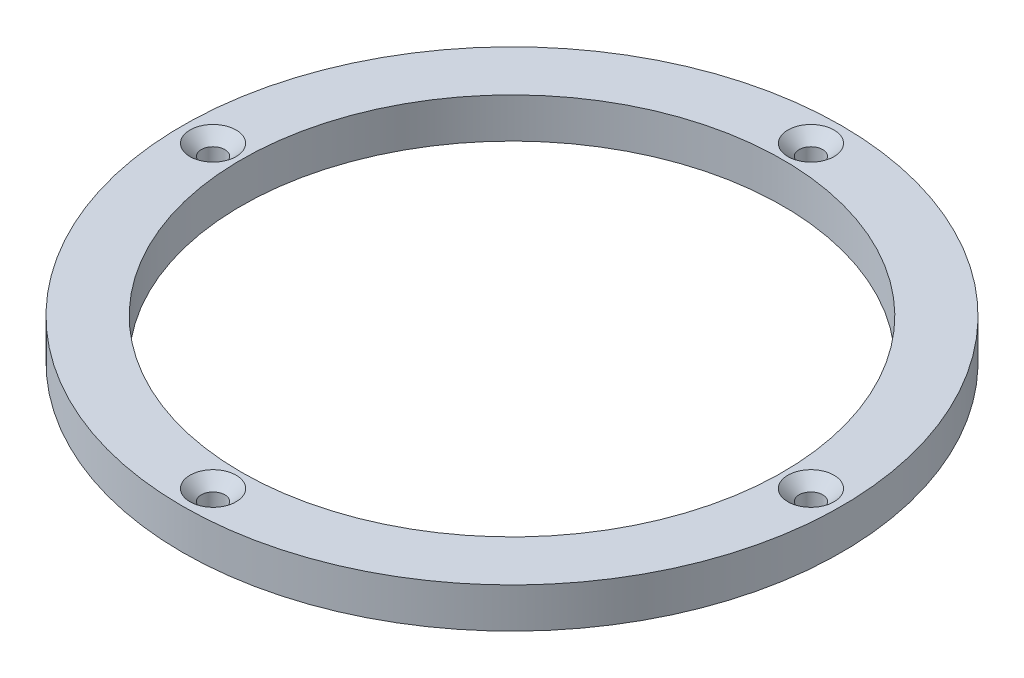
SolidWorks part; units mm, degrees
material "6061 合金"
ref_plane "前视基准面" through (0, 0, 0) normal (0, 0, 1) x (1, 0, 0)
ref_plane "上视基准面" through (0, 0, 0) normal (0, 1, 0) x (1, 0, 0)
ref_plane "右视基准面" through (0, 0, 0) normal (1, 0, 0) x (0, 0, -1)
other "Configuration Table"
sketch "草图1" plane through (0, 0, 0) normal (0, 1, 0) x (1, 0, 0)
  circle A0 centre (0, 0) radius 57.5
  circle A1 centre (0, 0) radius 70
  circle A2 centre (0, 0) radius 63.5 construction
  circle A3 centre (0, 63.5) radius 2.5
  circle A4 centre (63.5, 0) radius 2.5
  circle A5 centre (0, 0) radius 57.5
  circle A6 centre (0, -63.5) radius 2.5
  circle A7 centre (0, 0) radius 57.5
  circle A8 centre (-63.5, 0) radius 2.5
  circle A9 centre (0, 0) radius 57.5
  dimension "D1" = 127
  dimension "D2" = 140
  dimension "D3" = 115
  dimension "D4" = 5
  dimension "D5" = 4
extrude "凸台-拉伸1" add sketch "草图1" along normal blind 8.5 contours A1 A8 A6 A4 A3 A0 region at (-68.0201, 0, 0)
ref_axis "基准轴1" through (0, 8.5, -63.5) along (0, -1, 0)
ref_plane "基准面1" through (0, 0, -63.5) normal (0, 0, 1) x (1, 0, 0)
sketch "草图2" plane through (0, 0, -63.5) normal (0, 0, 1) x (1, 0, 0)
  line L0 (0, 0) -> (0, 8.5) construction
  line L1 (2.5, 8.5) -> (-2.5, 8.5) construction
  line L2 (0, 8.5) -> (4.9, 8.5)
  line L3 (70, 8.5) -> (-70, 8.5) construction
  line L4 (4.9, 8.5) -> (1.6, 5.2)
  line L5 (1.6, 5.2) -> (0, 5.2)
  line L6 (0, 5.2) -> (0, 8.5)
  dimension "D1" = 4.9
  dimension "D2" = 3.3
  dimension "D3" = 45
revolve "切除-旋转1" cut sketch "草图2" angle 360 about L0
pattern_circular "阵列(圆周)1" count 4 over 360 about axis through (0, 8.5, 0) along (0, -1, 0) of "切除-旋转1" reverse direction yes
